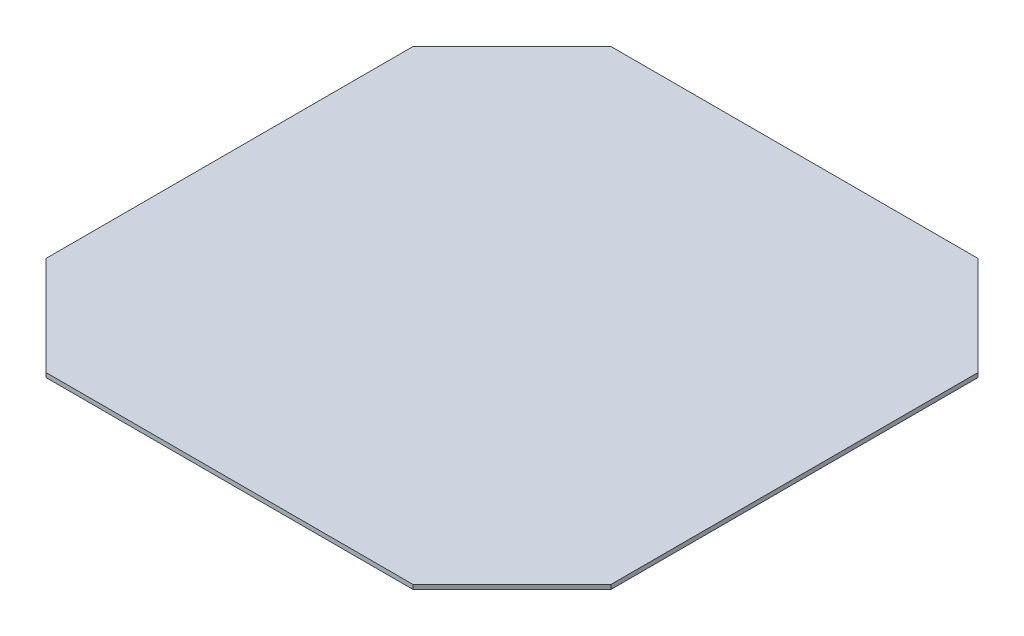
SolidWorks part; units mm, degrees
ref_plane "Front Plane" through (0, 0, 0) normal (0, 0, 1) x (1, 0, 0)
ref_plane "Top Plane" through (0, 0, 0) normal (0, 1, 0) x (1, 0, 0)
ref_plane "Right Plane" through (0, 0, 0) normal (1, 0, 0) x (0, 0, -1)
sketch "Sketch1" plane through (0, 0, 0) normal (0, 1, 0) x (1, 0, 0)
  line L0 (0, 615.95) -> (0, -615.95) construction
  line L1 (-615.95, 615.95) -> (615.95, 615.95)
  line L2 (-615.95, 615.95) -> (-615.95, -615.95)
  line L3 (-615.95, -615.95) -> (615.95, -615.95)
  line L4 (615.95, 615.95) -> (615.95, -615.95)
  dimension "D1" = 1231.9
  dimension "D2" = 1231.9
extrude "Boss-Extrude1" add sketch "Sketch1" along normal blind 9.525
sketch "Sketch2" plane through (0, 9.525, 0) normal (0, 1, 0) x (1, 0, 0)
  line L0 (0, -615.95) -> (0, 615.95) construction
  line L1 (-615.95, -615.95) -> (615.95, -615.95) construction
  line L2 (615.95, 615.95) -> (-615.95, 615.95) construction
  line L3 (-615.95, 0) -> (615.95, 0) construction
  line L4 (-615.95, 615.95) -> (-615.95, -615.95) construction
  line L5 (615.95, -615.95) -> (615.95, 615.95) construction
  circle A0 centre (-615.95, 615.95) radius 152.4
  circle A1 centre (-615.95, -615.95) radius 152.4
  circle A2 centre (615.95, -615.95) radius 152.4
  circle A3 centre (615.95, 615.95) radius 152.4
  point P20 (-615.95, 768.35)
  point P21 (-768.35, 615.95)
  dimension "D1" = 304.8
extrude "Cut-Extrude1" cut sketch "Sketch2" against normal up to next
sketch "Sketch3" plane through (0, 9.525, 0) normal (0, 1, 0) x (1, 0, 0)
  line L0 (400.4239, 615.95) -> (615.95, 400.4239)
  line L1 (463.55, 615.95) -> (-463.55, 615.95) construction
  line L2 (615.95, -463.55) -> (615.95, 463.55) construction
  line L3 (400.4239, 615.95) -> (615.95, 615.95) construction
  line L4 (615.95, 615.95) -> (615.95, 400.4239) construction
  circle A0 centre (615.95, 615.95) radius 152.4 construction
extrude "Cut-Extrude2" cut sketch "Sketch3" against normal through all and the other way through all
mirror "Mirror1" about plane through (0, 0, 0) normal (0, 0, 1) of "Cut-Extrude2"
mirror "Mirror2" about plane through (0, 0, 0) normal (1, 0, 0) of "Mirror1", "Cut-Extrude2"
